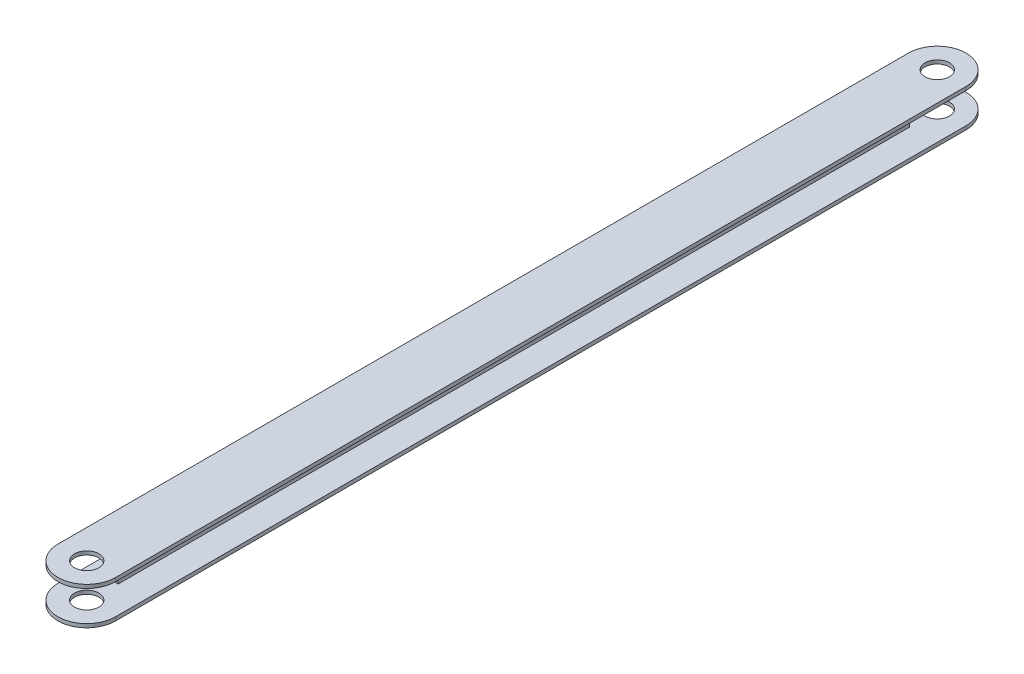
SolidWorks part; units mm, degrees
ref_plane "Front Plane" through (0, 0, 0) normal (0, 0, 1) x (1, 0, 0)
ref_plane "Top Plane" through (0, 0, 0) normal (0, 1, 0) x (1, 0, 0)
ref_plane "Right Plane" through (0, 0, 0) normal (1, 0, 0) x (0, 0, -1)
sketch "Sketch1" plane through (0, 0, 0) normal (0, 0, 1) x (1, 0, 0)
  line L0 (0, 0) -> (0, -5.6)
  line L1 (-0.6, 5) -> (0.6, 5)
  line L2 (-0.6, 5) -> (-0.6, -5)
  line L3 (-0.6, -5) -> (0.6, -5)
  line L4 (0.6, 5) -> (0.6, -5)
  line L5 (-0.6, 5) -> (0.6, -5) construction
  line L6 (-0.6, -5) -> (0.6, 5) construction
  line L7 (-9.5, -5) -> (9.5, -5)
  line L8 (-9.5, -5) -> (-9.5, -6.2)
  line L9 (-9.5, -6.2) -> (9.5, -6.2)
  line L10 (9.5, -5) -> (9.5, -6.2)
  line L11 (-9.5, -5) -> (9.5, -6.2) construction
  line L12 (-9.5, -6.2) -> (9.5, -5) construction
  line L13 (0, 0) -> (6.3315, 0) construction
  line L14 (-9.5, 6.2) -> (9.5, 5) construction
  line L15 (-9.5, 5) -> (9.5, 6.2) construction
  line L16 (9.5, 5) -> (9.5, 6.2)
  line L17 (-9.5, 6.2) -> (9.5, 6.2)
  line L18 (-9.5, 5) -> (-9.5, 6.2)
  line L19 (-9.5, 5) -> (9.5, 5)
  line L20 (-0.6, 5) -> (0.6, 5)
  point P0 (0, 0)
  point P6 (0, -5.6)
  point P19 (0, 5.6)
  dimension "D1" = 10
  dimension "D2" = 1.2
  dimension "D3" = 19
  dimension "D4" = 1.2
extrude "Boss-Extrude1" add sketch "Sketch1" along normal blind 299 contours L18 L19 L1 L16 L17 | L4 L1 L2 L3 | L10 L7 L3 L8 L9 region at (0, 5.6, 0) region at (0, 4.8993, 0) region at (-0.3, -5.1904, 0)
sketch "Sketch3" plane through (0, 6.2, 0) normal (0, 1, 0) x (1, 0, 0)
  line L0 (-9.5, 0) -> (9.5, 0) construction
  line L1 (-14.5, -9.5) -> (-9.5, -9.5)
  line L2 (9.5, -9.5) -> (14.5, -9.5)
  line L3 (9.5, -299) -> (9.5, 0) construction
  line L4 (-9.5, -299) -> (-9.5, 0) construction
  line L12 (9.5, -9.5) -> (4, -9.5)
  line L13 (-4, -9.5) -> (-9.5, -9.5)
  line L16 (-19.5, -309) -> (19.5, -309)
  line L17 (19.5, -309) -> (19.5, 10)
  line L18 (19.5, 10) -> (-19.5, 10)
  line L19 (-19.5, 10) -> (-19.5, -309)
  line L20 (-19.5, -309) -> (19.5, -309)
  line L21 (19.5, -309) -> (19.5, 10)
  line L22 (19.5, 10) -> (-19.5, 10)
  line L23 (-19.5, 10) -> (-19.5, -309)
  arc A0 (9.5, -9.5) -> (-9.5, -9.5) centre (0, -9.5) ccw
  circle A1 centre (0, -9.5) radius 4
  arc A2 (14.5, -9.5) -> (-14.5, -9.5) centre (0, -9.5) ccw
  point P11 (9.398, -9.5)
  point P12 (0, 0)
  point P15 (0, 0)
  line M5 (9.5, 0) -> (-9.5, 0)
  line M6 (-9.5, 0) -> (-9.5, -299)
  line M8 (9.5, -299) -> (9.5, 0)
  dimension "D1" = 9.5
  dimension "D2" = 10
  dimension "D3" = 5
ref_plane "Plane4" through (0, 0, 149.5) normal (0, 0, 1) x (1, 0, 0)
extrude "Cut-Extrude2" cut sketch "Sketch3" along direction (0, 1, 0) on the side against the normal blind 370 contours A0 M5 M6 | A0 M8 M5 | L2 A2 L1 M6 M5 M8 | A1 region at (0, 6.2, -4.6758) region at (-7.378, 6.2, 2.122) region at (0, 6.2, 9.5) region at (7.378, 6.2, 2.122)
mirror "Mirror1" about plane through (0, 0, 149.5) normal (0, 0, 1) of "Cut-Extrude2"
sketch "Sketch6" plane through (-0.6, 0, 0) normal (-1, 0, 0) x (0, 0, 1)
  line L0 (289.5, -5) -> (9.5, -5) construction
  line L1 (19.25, -5) -> (-0.25, -5)
  line L2 (19.25, -5) -> (19.25, 5)
  line L3 (19.25, 5) -> (-0.25, 5)
  line L4 (-0.25, -5) -> (-0.25, 5)
  line L5 (19.25, -5) -> (-0.25, 5) construction
  line L6 (19.25, 5) -> (-0.25, -5) construction
  line L7 (9.5, 5) -> (9.5, -5)
  point P0 (9.5, 0)
  point P6 (0, 0)
  point P7 (0, 0)
  line M3 (298.981, 5) -> (293.4547, 5)
  dimension "D1" = 19.5
extrude "Cut-Extrude4" cut sketch "Sketch6" along direction (1, 0, 0) on the side against the normal blind 370 contours L7 L3 L1 | L7 L1 L2 M3 region at (-0.6, 0, 14.375) region at (-0.6, 0, 4.625)
mirror "Mirror3" about plane through (0, 0, 149.5) normal (0, 0, 1) of "Cut-Extrude4"
